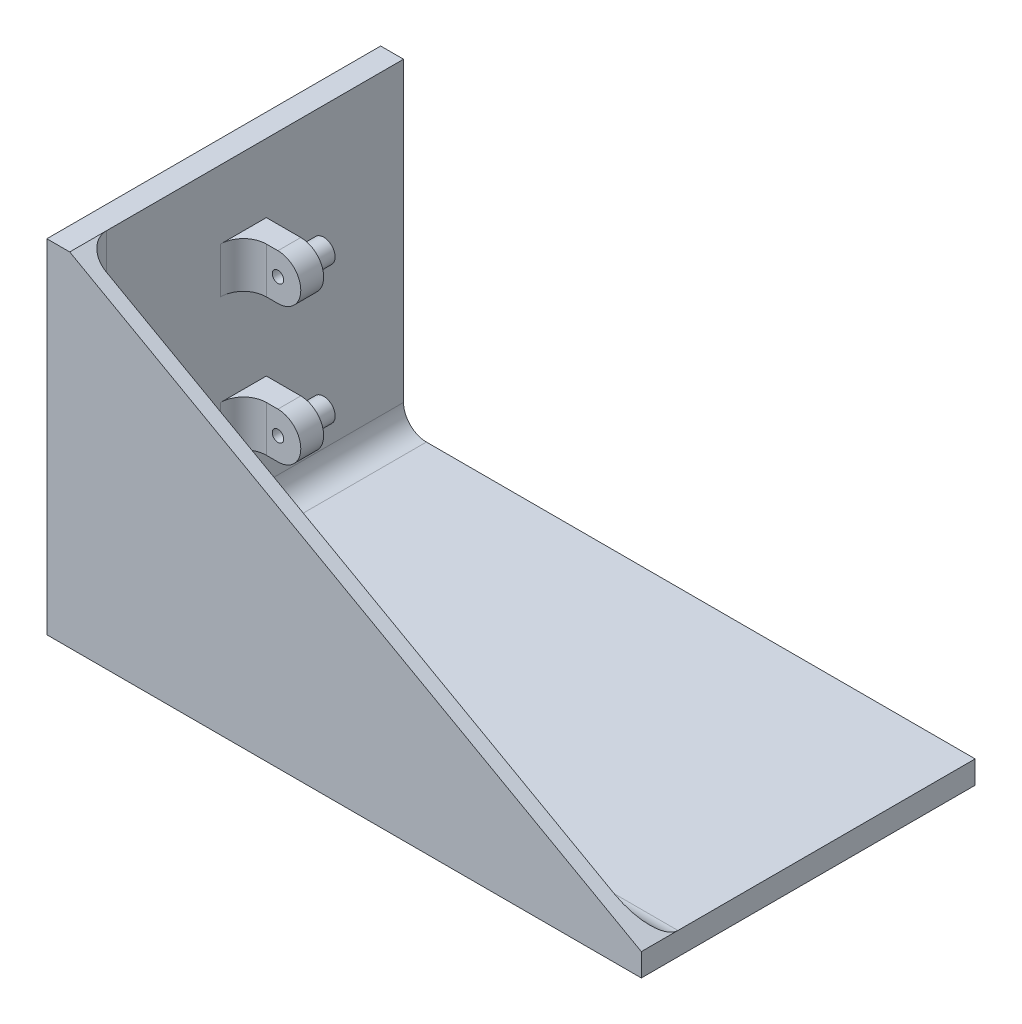
SolidWorks part; units mm, degrees
ref_plane "Piano frontale" through (0, 0, 0) normal (0, 0, 1) x (1, 0, 0)
ref_plane "Piano superiore" through (0, 0, 0) normal (0, 1, 0) x (1, 0, 0)
ref_plane "Piano destro" through (0, 0, 0) normal (1, 0, 0) x (0, 0, -1)
sketch "Schizzo1" plane through (0, 0, 0) normal (0, 0, 1) x (1, 0, 0)
  line L1 (0, 0) -> (-5, 0)
  line L2 (0, 0) -> (0, 70)
  line L3 (0, 70) -> (-5, 70)
  line L4 (-5, 0) -> (-5, 70)
  dimension "D1" = 70
  dimension "D2" = 5
extrude "Estrusione-Estrusione1" add sketch "Schizzo1" along normal blind 70
sketch "Schizzo2" plane through (0, 0, 70) normal (0, 0, 1) x (1, 0, 0)
  line L0 (0, 15) -> (0, 20)
  line L1 (0, 0) -> (0, 70) construction
  line L2 (0, 45) -> (0, 50)
  line L3 (7.5316, 55) -> (0, 55)
  line L4 (0, 55) -> (0, 45)
  line L5 (0, 45) -> (7.5316, 45)
  line L6 (7.5316, 25) -> (0, 25)
  line L7 (0, 25) -> (0, 15)
  line L8 (0, 15) -> (7.5316, 15)
  arc A0 (7.5316, 45) -> (7.5316, 55) centre (7.5316, 50) ccw
  arc A1 (7.5316, 15) -> (7.5316, 25) centre (7.5316, 20) ccw
  line M1 (0, 0) -> (0, 70)
  dimension "D1" = 10
  dimension "D2" = 10
extrude "Estrusione-Estrusione2" add sketch "Schizzo2" against normal blind 5 from offset 35 contours L5 A0 L3 M1 | L8 A1 L6 M1 region at (5.7836, 50, 70) region at (5.7836, 20, 70) offset against normal yes
sketch "Schizzo3" plane through (0, 0, 30) normal (0, 0, -1) x (-1, 0, 0)
  circle A0 centre (-7.5476, 50.0613) radius 2.5
  circle A1 centre (-7.5476, 19.9398) radius 2.5
  dimension "D1" = 5
  dimension "D2" = 5
extrude "Estrusione-Estrusione3" add sketch "Schizzo3" along normal blind 5
sketch "Schizzo4" plane through (0, 0, 0) normal (0, -1, 0) x (1, 0, 0)
  line L1 (-5, 0) -> (125, 0)
  line L2 (-5, 0) -> (-5, 70)
  line L3 (-5, 70) -> (125, 70)
  line L4 (125, 0) -> (125, 70)
extrude "Estrusione-Estrusione4" add sketch "Schizzo4" along normal blind 5
sketch "Schizzo5" plane through (0, 0, 25) normal (0, 0, -1) x (-1, 0, 0)
  circle A0 centre (-7.5476, 50.0613) radius 1.25
  circle A1 centre (-7.5476, 19.9398) radius 1.25
  dimension "D1" = 2.5
extrude "Taglio-Estrusione1" cut sketch "Schizzo5" against normal through all
sketch "Schizzo6" plane through (0, 0, 70) normal (0, 0, 1) x (1, 0, 0)
  line L0 (0, 70) -> (125, 0)
  line L7 (0, 0) -> (0, 70)
  line L8 (0, 70) -> (-5, 70)
  line L9 (-5, 70) -> (-5, -5)
  line L10 (-5, -5) -> (125, -5)
  line L11 (125, -5) -> (125, 0)
  line L12 (125, 0) -> (0, 0)
  line L13 (0, 0) -> (0, 70)
  line L14 (0, 70) -> (-5, 70)
  line L15 (-5, 70) -> (-5, -5)
  line L16 (-5, -5) -> (125, -5)
  line L17 (125, -5) -> (125, 0)
  line L18 (125, 0) -> (0, 0)
  line M7 (0, 0) -> (0, 70)
  line M8 (0, 70) -> (-5, 70)
  line M9 (-5, 70) -> (-5, -5)
  line M10 (-5, -5) -> (125, -5)
  line M11 (125, -5) -> (125, 0)
  line M12 (125, 0) -> (0, 0)
  dimension "D1" = 0
extrude "Estrusione-Estrusione5" add sketch "Schizzo6" along normal blind 3 contours M12 M7 M8 M9 M10 M11 | L0 M7 M12 region at (41.6667, 23.3333, 70) region at (-1.5008, 35, 70)
fillet "Raccordo1" radius 5 3 edges at (0, 0, 35) (0, 35, 70) (62.5, 0, 70)
fillet "Raccordo2" radius 5 2 edges at (0, 20, 35) (0, 50, 35)
